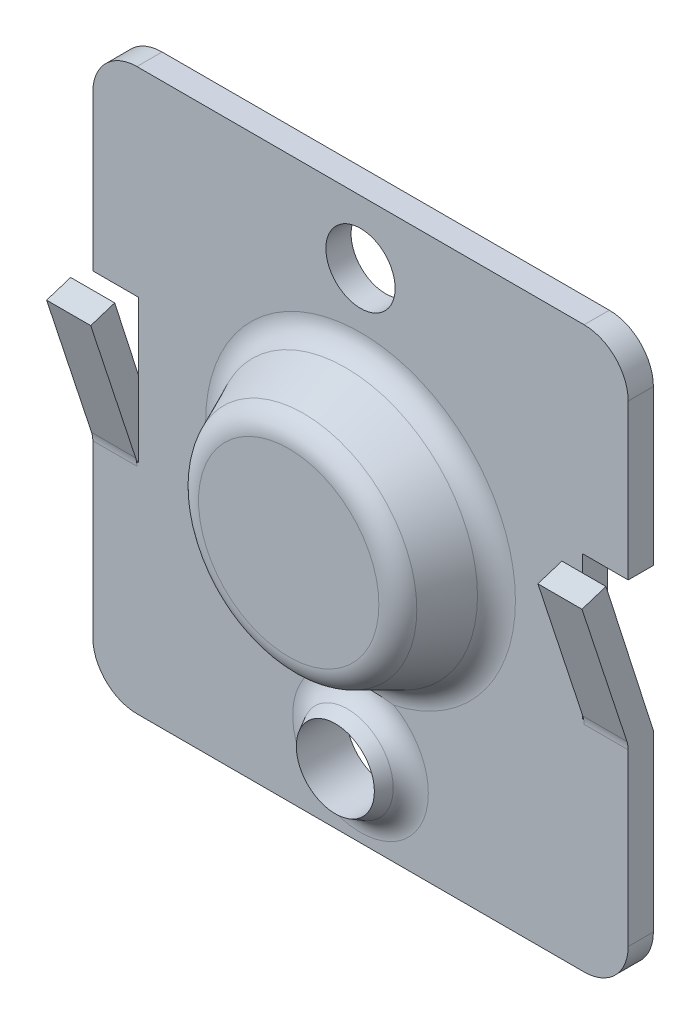
SolidWorks part; units mm, degrees
material "Plain Carbon Steel"
ref_plane "Front Plane" through (0, 0, 0) normal (0, 0, 1) x (1, 0, 0)
ref_plane "Top Plane" through (0, 0, 0) normal (0, 1, 0) x (1, 0, 0)
ref_plane "Right Plane" through (0, 0, 0) normal (1, 0, 0) x (0, 0, -1)
sketch "Sketch1" plane through (0, 0, 0) normal (0, 0, 1) x (1, 0, 0)
  line L0 (5.3975, 11.303) -> (5.3975, 0) construction
  line L1 (0.889, 0) -> (9.906, 0)
  line L2 (0, 0.889) -> (0, 4.405)
  line L3 (0.889, 11.303) -> (9.906, 11.303)
  line L4 (10.795, 0.889) -> (10.795, 4.405)
  line L5 (0, 7.2898) -> (0.9235, 7.2898)
  line L6 (0.9235, 7.2898) -> (0.9235, 4.405)
  line L7 (0.9235, 4.405) -> (0, 4.405)
  line L8 (9.8715, 4.405) -> (10.795, 4.405)
  line L9 (9.8715, 7.2898) -> (9.8715, 4.405)
  line L10 (10.795, 7.2898) -> (9.8715, 7.2898)
  line L11 (0, 7.2898) -> (0, 10.414)
  line L12 (10.795, 7.2898) -> (10.795, 10.414)
  circle A0 centre (5.3975, 10.033) radius 0.6985
  circle A1 centre (5.3975, 1.5494) radius 0.7874
  circle A2 centre (5.3975, 5.7912) radius 2.794 construction
  arc A3 (0.889, 0) -> (0, 0.889) centre (0.889, 0.889) cw
  arc A4 (9.906, 0) -> (10.795, 0.889) centre (9.906, 0.889) ccw
  arc A5 (9.906, 11.303) -> (10.795, 10.414) centre (9.906, 10.414) cw
  arc A6 (0, 10.414) -> (0.889, 11.303) centre (0.889, 10.414) cw
  point P23 (0, 0)
  point P26 (10.795, 0)
  point P31 (0, 11.303)
  dimension "D3" = 1.397
  dimension "D4" = 1.5748
  dimension "D6" = 5.588
  dimension "D7" = 4.2418
  dimension "D8" = 4.2418
  dimension "D10" = 0.889
  dimension "D1" = 10.795
  dimension "D2" = 11.303
  dimension "D5" = 5.7912
  dimension "D9" = 7.2898
extrude "Boss-Extrude1" add sketch "Sketch1" along normal blind 0.508
sketch "Sketch3" plane through (0, 0, 0.508) normal (0, 0, 1) x (1, 0, 0)
  circle A0 centre (5.3975, 5.7912) radius 2.794 construction
  circle A1 centre (5.3975, 5.7912) radius 2.794
ref_plane "Plane1" through (0, 0, 1.9558) normal (0, 0, 1) x (1, 0, 0)
sketch "Sketch4" plane through (0, 0, 1.9558) normal (0, 0, 1) x (1, 0, 0)
  circle A0 centre (5.3975, 5.7912) radius 2.1476
loft "Loft1" add profiles "Sketch3", "Sketch4" connector at (8.1915, 5.7912, 0.508) connector at (7.5451, 5.7912, 1.9558)
sketch "Sketch5" plane through (0, 0, 0.508) normal (0, 0, 1) x (1, 0, 0)
  circle A0 centre (5.3975, 1.5494) radius 1.067
ref_plane "Plane2" through (0, 0, 1.016) normal (0, 0, 1) x (1, 0, 0)
sketch "Sketch6" plane through (0, 0, 1.016) normal (0, 0, 1) x (1, 0, 0)
  circle A0 centre (5.3975, 1.5494) radius 0.7874
loft "Loft2" add profiles "Sketch5", "Sketch6" connector at (6.4645, 1.5494, 0.508) connector at (6.1849, 1.5494, 1.016)
sketch "Sketch7" plane through (0, 0, 1.016) normal (0, 0, 1) x (1, 0, 0)
  circle A1 centre (5.3975, 1.5494) radius 0.7874
  circle A2 centre (5.3975, 1.5494) radius 0.7874
  dimension "D1" = 0
extrude "Cut-Extrude1" cut sketch "Sketch7" against normal blind 0.508
sketch "Sketch9" plane through (0, 0, 0) normal (-1, 0, 0) x (0, 0, 1)
  line L0 (0, 4.405) -> (0.9561, 7.4)
  line L1 (0.9561, 7.4) -> (1.44, 7.2455)
  line L2 (1.44, 7.2455) -> (0.508, 4.405)
  line L3 (0.508, 4.405) -> (0, 4.405)
  line L4 (5.9372, 0) -> (-5.9372, 0) construction
  line L5 (0, -5.9372) -> (0, 5.9372) construction
  line L6 (0.508, 7.2898) -> (0, 7.2898) construction
  dimension "D1" = 7.4
  dimension "D2" = 1.44
extrude "Boss-Extrude2" add sketch "Sketch9" against normal blind 0.889
sketch "Sketch10" plane through (10.795, 0, 0) normal (1, 0, 0) x (0, 0, -1)
  line L0 (-1.44, 7.2455) -> (-0.508, 4.405) construction
  line L1 (-0.508, 4.405) -> (0, 4.405) construction
  line L2 (0, 4.405) -> (-0.9561, 7.4) construction
  line L3 (-0.9561, 7.4) -> (-1.44, 7.2455) construction
  line L4 (-1.44, 7.2455) -> (-0.508, 4.405)
  line L5 (-0.508, 4.405) -> (0, 4.405)
  line L6 (0, 4.405) -> (-0.9561, 7.4)
  line L7 (-0.9561, 7.4) -> (-1.44, 7.2455)
extrude "Boss-Extrude3" add sketch "Sketch10" against normal blind 0.889
fillet "Fillet1" radius 0.508 5 edges at (7.5451, 5.7912, 1.9558) (8.1915, 5.7912, 0.508) (6.4645, 1.5494, 0.508) (0.4445, 4.405, 0.508) (10.3505, 4.405, 0.508)
sketch "Sketch11" plane through (0, 0, 0) normal (0, 0, -1) x (-1, 0, 0)
  point P0 (-5.3975, 10.033)
other "CPoint1" parameters "Diameter"=0.69, "StubLength"=0
ref_axis "Axis1" through (5.3975, 10.033, -10) along (0, 0, 1)
